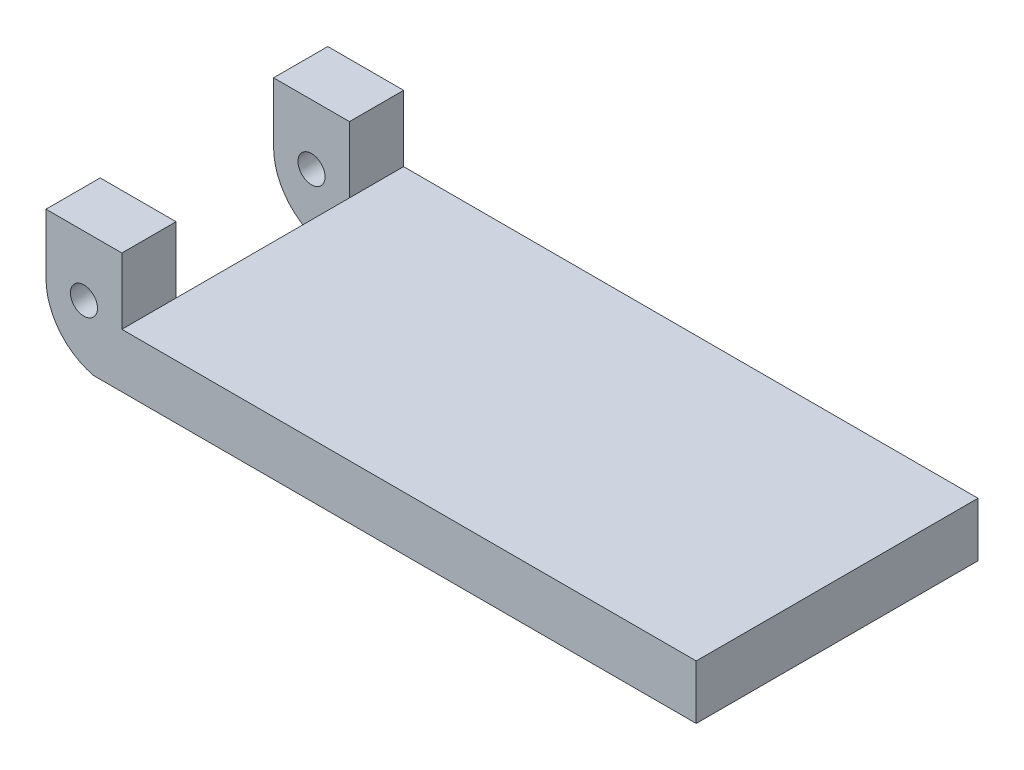
SolidWorks part; units mm, degrees
ref_plane "Front Plane" through (0, 0, 0) normal (0, 0, 1) x (1, 0, 0)
ref_plane "Top Plane" through (0, 0, 0) normal (0, 1, 0) x (1, 0, 0)
ref_plane "Right Plane" through (0, 0, 0) normal (1, 0, 0) x (0, 0, -1)
sketch "Sketch1" plane through (0, 0, 0) normal (0, 0, 1) x (1, 0, 0)
  line L1 (0, 0) -> (53, 0)
  line L2 (0, 0) -> (0, 5)
  line L3 (0, 5) -> (53, 5)
  line L4 (53, 0) -> (53, 5)
  dimension "D1" = 53
  dimension "D2" = 5
extrude "Boss-Extrude1" add sketch "Sketch1" along normal blind 13 and the other way blind 13
sketch "Sketch2" plane through (0, 0, 13) normal (0, 0, 1) x (1, 0, 0)
  line L1 (0, 11.1) -> (-7, 11.1)
  line L2 (0, 11.1) -> (0, 0)
  line L3 (0, 0) -> (-7, 0)
  line L4 (-7, 11.1) -> (-7, 0)
  line L5 (0, 0) -> (53, 0) construction
  line L6 (0, 5) -> (0, 0) construction
  dimension "D3" = 11.1
  dimension "D4" = 7
extrude "Boss-Extrude2" add sketch "Sketch2" against normal up to surface (26 mm away) up to face at (26.5, 2.5, -13)
sketch "Sketch3" plane through (0, 0, 0) normal (0, 0, 1) x (1, 0, 0)
  line L1 (0, 11.1) -> (-7, 11.1)
  line L2 (0, 11.1) -> (0, 0)
  line L3 (0, 0) -> (-7, 0)
  line L4 (-7, 11.1) -> (-7, 0)
extrude "Cut-Extrude1" cut sketch "Sketch3" against normal blind 8 and the other way blind 8
sketch "Sketch5" plane through (0, 0, 13) normal (0, 0, 1) x (1, 0, 0)
  line L0 (-7, 11.1) -> (-7, 0) construction
  line L1 (-7, 0) -> (53, 0) construction
  line L2 (-7, 0) -> (-2.6153, 0)
  line L3 (-7, 5.55) -> (-7, 0)
  arc A0 (-7, 5.55) -> (-2.6153, 0) centre (-1.3067, 5.5409) ccw
extrude "Cut-Extrude3" cut sketch "Sketch5" against normal up to surface (26 mm away) up to face at (19.75, 4.8583, -13)
sketch "Sketch6" plane through (0, 0, 13) normal (0, 0, 1) x (1, 0, 0)
  line L1 (-2.6153, 0) -> (53, 0) construction
  line L2 (0, 11.1) -> (-7, 11.1) construction
  line L3 (0, 11.1) -> (0, 0)
  line L4 (0, 0) -> (-7, 0) construction
  line L5 (-7, 11.1) -> (-7, 0) construction
  line L6 (0, 11.1) -> (-7, 0) construction
  line L7 (-7, 11.1) -> (0, 0) construction
  circle A1 centre (-3.5, 5.55) radius 1.25
  dimension "D1" = 2.5
extrude "Cut-Extrude5" cut sketch "Sketch6" against normal up to surface (26 mm away) contours A1 up to face at (16.4173, 4.8469, -13)
sketch "Sketch7" plane through (0, 0, 0) normal (0, -1, 0) x (1, 0, 0)
  line L0 (53, -13) -> (53, 13) construction
  line L1 (53, 10.16) -> (0, 10.16) construction
  line L2 (53, 10.16) -> (53, -10.16) construction
  line L3 (53, -10.16) -> (0, -10.16) construction
  line L4 (0, 10.16) -> (0, -10.16) construction
  line L5 (26.5, 10.16) -> (26.5, 3.555) construction
  line L6 (51.5, 3.555) -> (1.5, 3.555)
  line L7 (51.5, 3.555) -> (51.5, -3.555)
  line L8 (51.5, -3.555) -> (1.5, -3.555)
  line L9 (1.5, 3.555) -> (1.5, -3.555)
  line L10 (26.5, -3.555) -> (26.5, -10.16) construction
  line L11 (36.9641, 13) -> (36.9641, 10.16) construction
  line L12 (-2.6153, 13) -> (53, 13) construction
  line L13 (39.7244, -10.16) -> (39.7244, -13) construction
  line L14 (-2.6153, -13) -> (53, -13) construction
  line L15 (0, 8) -> (0, -8) construction
  line L16 (51.5, 0) -> (53, 0) construction
  line L17 (1.5, 0) -> (0, 0) construction
  dimension "D1" = 50
  dimension "D2" = 7.11
  dimension "D3" = 20.32
extrude "Boss-Extrude3" add sketch "Sketch7" along normal blind 0.5
